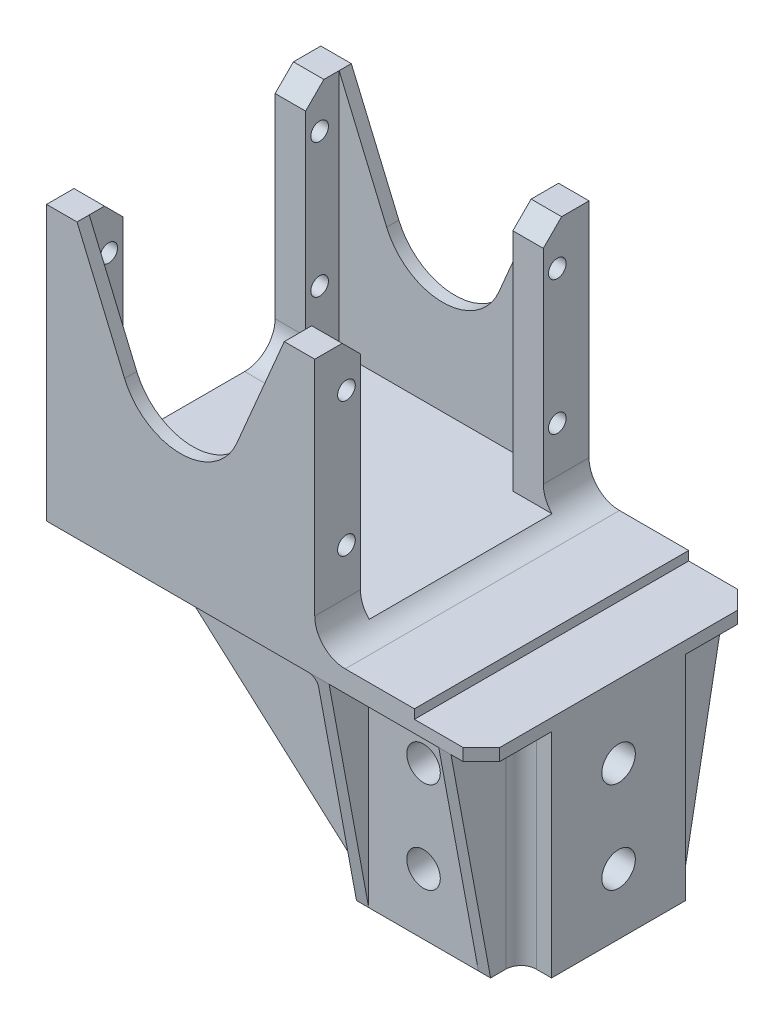
SolidWorks part; units mm, degrees
material "PLA"
ref_plane "Front Plane" through (0, 0, 0) normal (0, 0, 1) x (1, 0, 0)
ref_plane "Top Plane" through (0, 0, 0) normal (0, 1, 0) x (1, 0, 0)
ref_plane "Right Plane" through (0, 0, 0) normal (1, 0, 0) x (0, 0, -1)
sketch "Sketch2" plane through (0, 0, 0) normal (0, 0, 1) x (1, 0, 0)
  line L0 (12.8375, 22.5) -> (17.8375, 22.5) construction
  line L1 (-53.5125, 22.5) -> (17.8375, 22.5) construction
  line L2 (-17.8375, 22.5) -> (-17.8375, -22.5) construction
  line L3 (-53.5125, -22.5) -> (17.8375, -22.5)
  line L4 (17.8375, 22.5) -> (17.8375, -22.5) construction
  line L5 (-17.8375, 22.5) -> (17.8375, -22.5) construction
  line L6 (-17.8375, -22.5) -> (17.8375, 22.5) construction
  line L7 (-48.5125, 22.5) -> (12.8375, 22.5) construction
  line L8 (-17.8375, 22.5) -> (-17.8375, -17.5) construction
  line L9 (-48.5125, -17.5) -> (12.8375, -17.5) construction
  line L10 (12.8375, 22.5) -> (12.8375, -17.5) construction
  line L11 (-17.8375, 22.5) -> (12.8375, -17.5) construction
  line L12 (-17.8375, -17.5) -> (12.8375, 22.5) construction
  line L14 (-17.8375, -17.5) -> (-48.5125, 22.5) construction
  line L15 (-17.8375, 22.5) -> (-48.5125, -17.5) construction
  line L16 (-17.8375, -22.5) -> (-53.5125, 22.5) construction
  line L17 (-17.8375, 22.5) -> (-53.5125, -22.5) construction
  line L18 (-48.5125, 22.5) -> (-48.5125, -17.5)
  line L19 (-53.5125, 22.5) -> (-53.5125, -22.5)
  line L20 (-48.5125, 22.5) -> (-53.5125, 22.5)
  line L22 (-9.5125, -17.5) -> (-9.5125, 22.5)
  line L23 (-9.5125, 22.5) -> (-14.5125, 22.5)
  line L24 (-14.5125, 22.5) -> (-14.5125, -17.5)
  line L26 (17.8375, -17.5) -> (17.8375, -22.5)
  line L27 (-48.5125, -17.5) -> (-14.5125, -17.5)
  line L28 (-9.5125, -17.5) -> (17.8375, -17.5)
  point P4 (0, 0)
  point P8 (-2.5, 2.5)
  point P14 (-33.175, 2.5)
  point P15 (-35.675, 0)
  dimension "D1" = 5
  dimension "D2" = 40
  dimension "D3" = 27.35
  dimension "D4" = 5
  dimension "D5" = 34
  dimension "D6" = 5
extrude "Boss-Extrude1" add sketch "Sketch2" along normal blind 45
sketch "Sketch3" plane through (-53.5125, 0, 0) normal (1, 0, 0) x (0, 0, -1)
  line L0 (-5.2, 22.5) -> (-5.2, -22.5) construction
  line L2 (-39.8, 22.5) -> (-39.8, -22.5) construction
  line L4 (-37.5, 22.5) -> (-7.5, 22.5)
  line L5 (-37.5, 22.5) -> (-37.5, -17.5)
  line L6 (-37.5, -17.5) -> (-7.5, -17.5)
  line L7 (-7.5, 22.5) -> (-7.5, -17.5)
  line L8 (-37.5, 22.5) -> (-7.5, -17.5) construction
  line L9 (-37.5, -17.5) -> (-7.5, 22.5) construction
  line L10 (-45, 22.5) -> (0, 22.5) construction
  line L11 (-39.8, 15.5) -> (-5.2, 15.5) construction
  line L12 (-39.8, -6.5) -> (-5.2, -6.5) construction
  line L13 (-45, -22.5) -> (0, -22.5) construction
  circle A2 centre (-5.2, 15.5) radius 1.25 construction
  circle A3 centre (-5.2, -6.5) radius 1.25 construction
  circle A4 centre (-39.8, 15.5) radius 1.25 construction
  circle A5 centre (-39.8, -6.5) radius 1.25 construction
  point P10 (-22.5, 2.5)
  dimension "D4" = 2.3
  dimension "D7" = 2.5
  dimension "D5" = 2.5
  dimension "D6" = 2.5
  dimension "D9" = 2.5
  dimension "D8" = 22
  dimension "D1" = 30
  dimension "D2" = 5
  dimension "D3" = 2.3
  dimension "D10" = 11
extrude "Cut-Extrude1" cut sketch "Sketch3" along normal through all
sketch "Sketch4" plane through (0, -22.5, 0) normal (0, -1, 0) x (1, 0, 0)
  line L0 (-53.5125, 22.5) -> (17.8375, 22.5) construction
  line L1 (17.8375, 45) -> (17.8375, 0) construction
  line L3 (-53.5125, 45) -> (-53.5125, 0) construction
  line L10 (-8.4125, 32.75) -> (12.0875, 32.75)
  line L11 (-8.4125, 32.75) -> (-8.4125, 12.25)
  line L12 (-8.4125, 12.25) -> (12.0875, 12.25)
  line L13 (12.0875, 32.75) -> (12.0875, 12.25)
  line L14 (-8.4125, 32.75) -> (12.0875, 12.25) construction
  line L15 (-8.4125, 12.25) -> (12.0875, 32.75) construction
  line L16 (-14.1625, 38.5) -> (17.8375, 38.5)
  line L17 (-14.1625, 38.5) -> (-14.1625, 6.5)
  line L18 (-14.1625, 6.5) -> (17.8375, 6.5)
  line L19 (17.8375, 38.5) -> (17.8375, 6.5)
  line L20 (-14.1625, 38.5) -> (17.8375, 6.5) construction
  line L21 (-14.1625, 6.5) -> (17.8375, 38.5) construction
  circle A0 centre (1.8375, 22.5) radius 2.5
  point P18 (1.8375, 22.5)
  point P23 (1.8375, 22.5)
  dimension "D1" = 5
  dimension "D2" = 20.5
  dimension "D3" = 20.5
  dimension "D4" = 32
extrude "Boss-Extrude2" add sketch "Sketch4" along normal blind 35 contours L19 L16 L17 L18 L10 L13 L12 L11 region at (1.8375, -22.5, 38.0475)
sketch "Sketch5" plane through (0, 0, 38.5) normal (0, 0, 1) x (1, 0, 0)
  line L0 (1.8375, -22.5) -> (1.8375, -57.5) construction
  line L3 (-14.1625, -22.5) -> (17.8375, -22.5) construction
  line L4 (-14.1625, -57.5) -> (17.8375, -57.5) construction
  circle A0 centre (1.8375, -32.5) radius 2.5 construction
  circle A1 centre (1.8375, -47.5) radius 2.5 construction
  dimension "D2" = 5
  dimension "D3" = 5
  dimension "D4" = 10
  dimension "D1" = 15
sketch "Sketch6" plane through (0, -57.5, 0) normal (0, -1, 0) x (-1, 0, 0)
  line L1 (14.1625, -38.5) -> (9.1625, -38.5)
  line L2 (14.1625, -38.5) -> (14.1625, -33.5)
  line L3 (14.1625, -33.5) -> (9.1625, -33.5)
  line L4 (9.1625, -38.5) -> (9.1625, -33.5)
  line L5 (14.1625, -38.5) -> (9.1625, -33.5) construction
  line L6 (14.1625, -33.5) -> (9.1625, -38.5) construction
  line L7 (-17.8375, -38.5) -> (-12.8375, -38.5)
  line L8 (-17.8375, -38.5) -> (-17.8375, -33.5)
  line L9 (-17.8375, -33.5) -> (-12.8375, -33.5)
  line L10 (-12.8375, -38.5) -> (-12.8375, -33.5)
  line L11 (-17.8375, -38.5) -> (-12.8375, -33.5) construction
  line L12 (-17.8375, -33.5) -> (-12.8375, -38.5) construction
  line L13 (-17.8375, -6.5) -> (-12.8375, -6.5)
  line L14 (-17.8375, -6.5) -> (-17.8375, -11.5)
  line L15 (-17.8375, -11.5) -> (-12.8375, -11.5)
  line L16 (-12.8375, -6.5) -> (-12.8375, -11.5)
  line L17 (-17.8375, -6.5) -> (-12.8375, -11.5) construction
  line L18 (-17.8375, -11.5) -> (-12.8375, -6.5) construction
  line L19 (14.1625, -6.5) -> (9.1625, -6.5)
  line L20 (14.1625, -6.5) -> (14.1625, -11.5)
  line L21 (14.1625, -11.5) -> (9.1625, -11.5)
  line L22 (9.1625, -6.5) -> (9.1625, -11.5)
  line L23 (14.1625, -6.5) -> (9.1625, -11.5) construction
  line L24 (14.1625, -11.5) -> (9.1625, -6.5) construction
  point P4 (11.6625, -36)
  point P11 (-15.3375, -36)
  point P18 (-15.3375, -9)
  point P25 (11.6625, -9)
  dimension "D1" = 5
  dimension "D2" = 5
  dimension "D3" = 5
  dimension "D4" = 5
extrude "Cut-Extrude4" cut sketch "Sketch6" against normal up to surface (35 mm away) up to face at (-8, -22.5, 22.5)
sketch "Sketch9" plane through (0, 0, 33.5) normal (0, 0, 1) x (1, 0, 0)
  line L0 (-14.1625, -57.5) -> (-53.5125, -22.5)
  line L1 (-53.5125, -22.5) -> (17.8375, -22.5) construction
  line L2 (-53.5125, -22.5) -> (17.8375, -22.5) construction
rib "Rib1" sketch "Sketch9" sketch "Sketch9" thickness 2 extrusion direction parallel to sketch draft on no parameters "D1"=2
pattern_linear "LPattern1" count 2 spacing 20 along (0, 0, -1) of "Rib1"
sketch "Sketch14" plane through (12.8375, 0, 0) normal (1, 0, 0) x (0, 0, -1)
  line L0 (-6.5, -57.5) -> (0, -22.5)
rib "Rib6" sketch "Sketch14" sketch "Sketch14" thickness 2 extrusion direction parallel to sketch draft on no parameters "D1"=2
sketch "Sketch15" plane through (-9.1625, 0, 0) normal (-1, 0, 0) x (0, 0, 1)
  line L0 (6.5, -57.5) -> (0, -22.5)
rib "Rib7" sketch "Sketch15" sketch "Sketch15" thickness 2 extrusion direction parallel to sketch draft on no parameters "D1"=2
fillet "Fillet2" radius 5 3 edges at (-14.1625, -22.5, 22.5) (1.8375, -22.5, 6.5) (1.8375, -22.5, 38.5)
fillet "Fillet3" radius 5 2 edges at (-9.5125, -17.5, 3.75) (-9.5125, -17.5, 41.25)
sketch "Sketch17" plane through (0, 0, 45) normal (0, 0, 1) x (1, 0, 0)
  line L0 (-48.5125, 22.5) -> (-31.5125, -17.5)
  line L1 (-14.5125, -17.5) -> (-48.5125, -17.5) construction
rib "Rib10" sketch "Sketch17" sketch "Sketch17" thickness 2 extrusion direction parallel to sketch draft on no parameters "D1"=2
sketch "Sketch18" plane through (0, 0, 45) normal (0, 0, 1) x (1, 0, 0)
  line L0 (-31.5125, -17.5) -> (-14.5125, 22.5)
rib "Rib11" sketch "Sketch18" sketch "Sketch18" thickness 2 extrusion direction parallel to sketch draft on no parameters "D1"=2
fillet "Fillet4" radius 10 1 edges at (-31.5125, -17.5, 44)
pattern_linear "LPattern2" count 2 spacing 43 along (0, 0, -1) of "Fillet4", "Rib11", "Rib10"
hole_wizard "M5 Clearance Hole2" positions "Sketch20" profile "Sketch22" hole size "M5" standard "ISO"
sketch "Sketch20" plane through (0, 0, 38.5) normal (0, 0, 1) x (1, 0, 0)
  point P0 (1.8375, -32.5)
  point P3 (1.8375, -47.5)
sketch "Sketch22" plane through (1.8375, -32.5, 38.5) normal (1, 0, 0) x (0, -1, 0)
  line L0 (0, 0) -> (0, 7.6524)
  line L1 (0, 7.6524) -> (2.75, 6)
  line L2 (2.75, 6) -> (2.75, 0)
  line L5 (2.75, 0) -> (0, 0)
  line L10 (0, 7.6524) -> (-2.75, 6) construction
  line L11 (0, -6.35) -> (0, 107.95) construction
  dimension "Hole Dia." = 5.5
  dimension "Hole Depth" = 6
  dimension "Drill Angle" = 118
hole_wizard "M2.5 Clearance Hole1" positions "Sketch23" profile "Sketch24" hole size "M2.5" standard "ISO" end condition through all
sketch "Sketch23" plane through (-53.5125, 0, 0) normal (-1, 0, 0) x (0, 0, 1)
  point P0 (5.2, 15.5)
  point P3 (39.8, 15.5)
  point P6 (39.8, -6.5)
  point P9 (5.2, -6.5)
sketch "Sketch24" plane through (-53.5125, 15.5, 5.2) normal (0, 1, 0) x (0, 0, 1)
  line L0 (0, 0) -> (0, 71.35)
  line L1 (0, 71.35) -> (1.45, 71.35)
  line L2 (1.45, 71.35) -> (1.45, 0)
  line L5 (1.45, 0) -> (0, 0)
  line L11 (0, -6.35) -> (0, 107.95) construction
  dimension "Thru Hole Dia." = 2.9
  dimension "Thru Hole Depth" = 71.35
fillet "Fillet5" radius 2.5 4 edges at (-9.1625, -40, 11.5) (-9.1625, -40, 33.5) (12.8375, -40, 33.5) (12.8375, -40, 11.5)
extrude "Boss-Extrude4" add sketch "Sketch4<4>" along normal blind 8 contours A0 region at (1.8375, -22.5, 22.5)
sketch "Sketch4<4>" plane through (0, -22.5, 0) normal (0, -1, 0) x (1, 0, 0) same geometry as "Sketch4"
pattern_circular "CirPattern1" count 4 every 90 about axis through (1.8375, -30.5, 22.5) along (0, -1, 0) of "M5 Clearance Hole2"
ref_axis "Axis2" through (1.8375, -30.5, 22.5) along (0, 1, 0)
ref_plane "Plane1" through (0, 0, 22.5) normal (0, 0, 1) x (1, 0, 0)
mirror "Mirror1" about plane through (0, 0, 22.5) normal (0, 0, 1) of "Rib6", "Rib7"
chamfer "Chamfer1" distance 3 angle 45 6 edges at (17.8375, -20, 0) (17.8375, -20, 45) (-51.0125, 22.5, 37.5) (-51.0125, 22.5, 7.5) (-12.0125, 22.5, 7.5) (-12.0125, 22.5, 37.5)
fillet "Fillet6" radius 5 2 edges at (-51.0125, -17.5, 37.5) (-51.0125, -17.5, 7.5)
fillet "Fillet7" radius 1.5 12 edges at (-9.1625, -22.5, 4.5) (-9.8947, -22.5, 10.7678) (-14.1625, -42.5, 13.5) (-15.627, -23.9645, 13.5) (-14.1625, -42.5, 31.5) (-15.627, -23.9645, 31.5) (-9.1625, -22.5, 40.5) (-9.8947, -22.5, 34.2322) (-32.5875, -22.5, 11.5) (-36.3375, -22.5, 13.5) (-36.3375, -22.5, 31.5) (-32.5875, -22.5, 33.5)
sketch "Sketch27" plane through (0, 0, 45) normal (0, 0, 1) x (1, 0, 0)
  line L0 (17.8375, -17.5) -> (17.8375, -22.5) construction
  line L1 (-9.5125, -12.5) -> (17.8375, -12.5)
  line L2 (-9.5125, -12.5) -> (-9.5125, -19)
  line L3 (-9.5125, -19) -> (17.8375, -19)
  line L4 (17.8375, -12.5) -> (17.8375, -19)
  line L5 (10.8375, -22.5) -> (12.8375, -22.5) construction
  dimension "D1" = 3.5
extrude "Cut-Extrude6" cut sketch "Sketch27" against normal through all
fillet "Fillet8" radius 5 1 edges at (-9.5125, -19, 22.5)
sketch "Sketch29" plane through (0, -19, 0) normal (0, 1, 0) x (1, 0, 0)
  line L0 (-4.5125, 0) -> (14.8375, 0) construction
  line L1 (17.8375, -45) -> (6.8375, -45)
  line L2 (17.8375, -45) -> (17.8375, 0)
  line L3 (17.8375, 0) -> (6.8375, 0)
  line L4 (6.8375, -45) -> (6.8375, 0)
  line L5 (17.8375, -45) -> (6.8375, 0) construction
  line L6 (17.8375, 0) -> (6.8375, -45) construction
  line L7 (-4.5125, -45) -> (14.8375, -45) construction
  line L8 (17.8375, -3) -> (17.8375, -42) construction
  point P0 (12.3375, -22.5)
  dimension "D1" = 11
extrude "Cut-Extrude7" cut sketch "Sketch29" against normal blind 1.5
